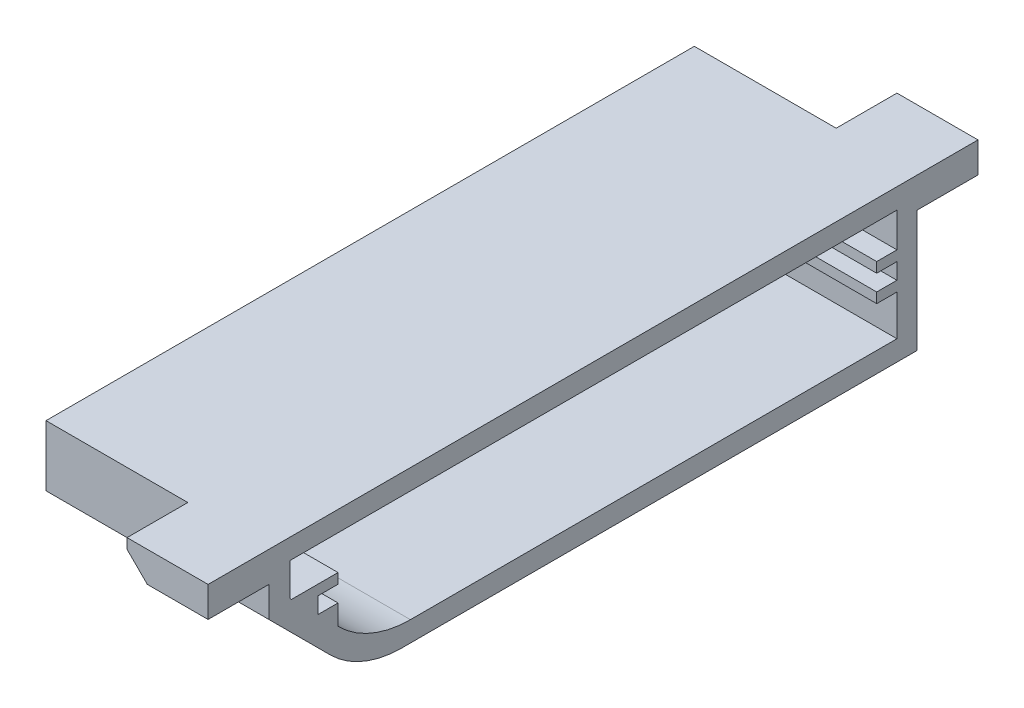
SolidWorks part; units mm, degrees
ref_plane "前视基准面" through (0, 0, 0) normal (0, 0, 1) x (1, 0, 0)
ref_plane "上视基准面" through (0, 0, 0) normal (0, 1, 0) x (1, 0, 0)
ref_plane "右视基准面" through (0, 0, 0) normal (1, 0, 0) x (0, 0, -1)
sketch "草图1" plane through (0, 0, 0) normal (0, 0, 1) x (1, 0, 0)
  line L0 (0, 0) -> (22, 0)
  line L1 (0, 0) -> (0, 15)
  line L2 (0, 15) -> (22, 15)
  line L3 (22, 15) -> (22, 0)
extrude "凸台-拉伸1" add sketch "草图1" along normal blind 2
sketch "草图2" plane through (0, 0, 0) normal (0, -1, 0) x (1, 0, 0)
  line L0 (0, 0) -> (0, 30)
  line L2 (22, 0) -> (22, 30)
  line L3 (22, 30) -> (0, 30)
  line L4 (0, 0) -> (22, 0)
extrude "凸台-拉伸2" add sketch "草图2" against normal blind 2
sketch "草图3" plane through (0, 0, 0) normal (-1, 0, 0) x (0, 0, 1)
  line L0 (0, 15) -> (64, 15)
  line L3 (0, 15) -> (0, 0) construction
  line L4 (0, 13) -> (0, 15)
  line L5 (64, 15) -> (64, 9)
  line L6 (64, 8) -> (64, 15) construction
  line L7 (30, 2) -> (53.4794, 2)
  line L8 (61.932, 10.4526) -> (61.932, 13)
  line L10 (30, 2) -> (30, 0)
  line L11 (61.932, 13) -> (0, 13)
  line L12 (30, 0) -> (55, 0)
  line L13 (64, 9) -> (55, 0)
  line L14 (60.9069, 8.7353) -> (60.9069, 8.7353)
  line L15 (60.9069, 8.7353) -> (60.9069, 8.7353)
  line L16 (60.9069, 8.7353) -> (60.9069, 8.7353)
  line L17 (60.9069, 8.7353) -> (60.9069, 8.7353)
  line L18 (60.9069, 8.7353) -> (60.9069, 8.7353)
  line L19 (60.9069, 8.7353) -> (55.1967, 3.0251)
  line L20 (55.1967, 3.0251) -> (55.1967, 3.0251)
  line L21 (55.1967, 3.0251) -> (55.1967, 3.0251)
  line L22 (55.1967, 3.0251) -> (55.1967, 3.0251)
  line L23 (60.9069, 8.7353) -> (61.932, 9.7604)
  line L24 (61.932, 9.7604) -> (61.932, 10.4526)
  line L25 (55.1967, 3.0251) -> (54.1716, 2)
  line L26 (54.1716, 2) -> (53.4794, 2)
  line M4 (30, 0) -> (30, 2)
  line M6 (2, 2) -> (2, 15)
  line M7 (2, 15) -> (0, 15)
  line M8 (0, 15) -> (0, 0)
  dimension "D1" = 2
extrude "凸台-拉伸3" add sketch "草图3" against normal blind 22 contours L11 L8 L5 L0 M4 M6 | L11 M6 M7 M8 region at (0, 14, 1) region at (0, 14.3621, 33)
sketch "草图4" plane through (0, 0, 64) normal (0, 0, 1) x (1, 0, 0)
  line L1 (22, 15) -> (14, 15)
  line L2 (22, 15) -> (22, 12)
  line L3 (22, 12) -> (14, 12)
  line L4 (14, 15) -> (14, 12)
extrude "凸台-拉伸4" add sketch "草图4" along normal blind 6
sketch "草图5" plane through (0, 0, 0) normal (0, 0, -1) x (-1, 0, 0)
  line L1 (-22, 15) -> (-14, 15)
  line L2 (-22, 15) -> (-22, 12)
  line L3 (-22, 12) -> (-14, 12)
  line L4 (-14, 15) -> (-14, 12)
extrude "凸台-拉伸5" add sketch "草图5" along normal blind 6
chamfer "倒角1" distance 2 angle 45 2 edges at (14, 12, 67) (14, 12, -3)
sketch "草图6" plane through (0, 0, 0) normal (-1, 0, 0) x (0, 0, 1)
  line L0 (57.1716, 7) -> (59.1716, 7)
  line L1 (2, 13) -> (2, 2) construction
  line L2 (2, 6) -> (4, 6)
  line L3 (4, 6) -> (4, 7)
  line L4 (4, 7) -> (2, 7)
  line L5 (2, 9.6) -> (2, 8.6)
  line L6 (2, 8.6) -> (4, 8.6)
  line L7 (4, 8.6) -> (4, 9.6)
  line L8 (4, 9.6) -> (2, 9.6)
  line L9 (2, 7) -> (2, 6)
  line L10 (57.1716, 7) -> (57.1716, 5)
  line L11 (61.932, 9.7604) -> (54.1716, 2) construction
  line L19 (59.1716, 7) -> (59.1716, 8.6)
  line L20 (59.1716, 8.6) -> (57.1716, 8.6)
  line L21 (57.1716, 8.6) -> (57.1716, 9.6)
  line L22 (57.1716, 9.6) -> (61.7716, 9.6)
  line L25 (57.1716, 5) -> (59.1716, 5)
  line L26 (59.1716, 5) -> (59.1716, 6.3165)
  line L27 (59.1716, 6.3165) -> (60.5136, 6.3165)
  line L28 (60.5136, 6.3165) -> (60.5136, 7.9254)
  line L29 (60.5136, 7.9254) -> (61.7716, 7.9254)
  line L30 (61.7716, 7.9254) -> (61.7716, 9.6)
extrude "凸台-拉伸6" add sketch "草图6" against normal blind 22
fillet "圆角1" radius 10 2 edges at (11, 0, 55) (11, 2, 54.1716)
